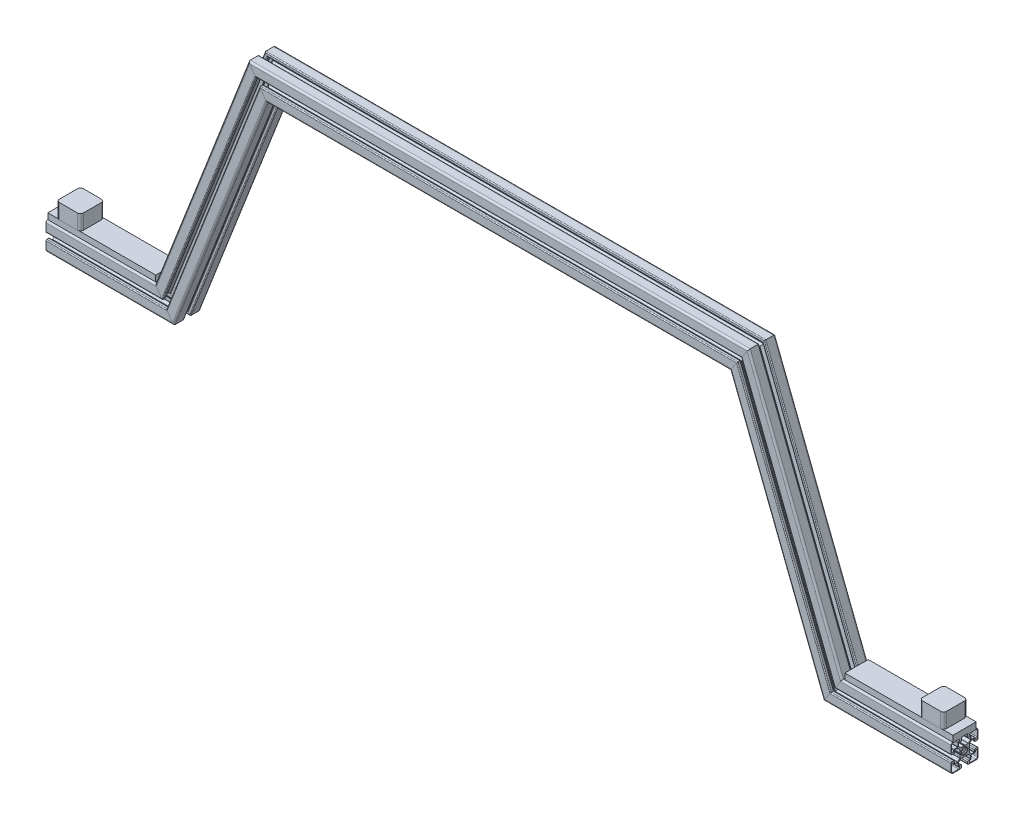
SolidWorks part; units mm, degrees
material "Commercially Pure CP-Ti UNS R50400 (SS)"
ref_plane "Front Plane" through (0, 0, 0) normal (0, 0, 1) x (1, 0, 0)
ref_plane "Top Plane" through (0, 0, 0) normal (0, 1, 0) x (1, 0, 0)
ref_plane "Right Plane" through (0, 0, 0) normal (1, 0, 0) x (0, 0, -1)
sketch "Sketch5" plane through (0, 0, 0) normal (1, 0, 0) x (0, 0, -1)
  line L0 (13.9698, 21.2743) -> (13.5298, 21.2743)
  line L1 (12.0298, 22.7743) -> (12.0298, 23.2743)
  line L2 (13.5298, 24.7743) -> (23.1398, 24.7743)
  line L3 (25.4198, 22.4943) -> (25.4198, 12.8843)
  line L4 (23.9198, 11.3843) -> (23.4198, 11.3843)
  line L5 (21.9198, 12.8843) -> (21.9198, 13.3243)
  line L6 (20.9198, 14.3243) -> (15.3498, 14.3243)
  line L7 (14.9698, 14.7043) -> (14.9698, 20.2743)
  line L8 (21.9589, -6.6897) -> (21.9589, -6.2497)
  line L9 (23.4589, -4.7497) -> (23.9589, -4.7497)
  line L10 (25.4589, -6.2497) -> (25.4589, -15.8597)
  line L11 (23.1789, -18.1397) -> (13.5689, -18.1397)
  line L12 (12.0689, -16.6397) -> (12.0689, -16.1397)
  line L13 (13.5689, -14.6397) -> (14.0089, -14.6397)
  line L14 (15.0089, -13.6397) -> (15.0089, -8.0697)
  line L15 (15.3889, -7.6897) -> (20.9589, -7.6897)
  line L16 (-6.0052, -14.6787) -> (-5.5652, -14.6787)
  line L17 (-4.0652, -16.1787) -> (-4.0652, -16.6787)
  line L18 (-5.5652, -18.1787) -> (-15.1752, -18.1787)
  line L19 (-17.4552, -15.8987) -> (-17.4552, -6.2887)
  line L20 (-15.9552, -4.7887) -> (-15.4552, -4.7887)
  line L21 (-13.9552, -6.2887) -> (-13.9552, -6.7287)
  line L22 (-12.9552, -7.7287) -> (-7.3852, -7.7287)
  line L23 (-7.0052, -8.1087) -> (-7.0052, -13.6787)
  line L24 (1.8289, -2.4886) -> (1.4132, -2.3164)
  line L25 (-1.632, 0.7289) -> (-1.8042, 1.1447)
  line L26 (-1.804, 5.4512) -> (-1.6318, 5.867)
  line L27 (1.4134, 8.9121) -> (1.8292, 9.0843)
  line L28 (6.1358, 9.0842) -> (6.5515, 8.912)
  line L29 (9.5966, 5.8667) -> (9.7688, 5.451)
  line L30 (9.7687, 1.1444) -> (9.5965, 0.7287)
  line L31 (6.5512, -2.3165) -> (6.1355, -2.4887)
  line L32 (-13.9942, 13.2853) -> (-13.9942, 12.8453)
  line L33 (-15.4942, 11.3453) -> (-15.9942, 11.3453)
  line L34 (-17.4942, 12.8453) -> (-17.4942, 22.4553)
  line L35 (-15.2142, 24.7353) -> (-5.6042, 24.7353)
  line L36 (-4.1042, 23.2353) -> (-4.1042, 22.7353)
  line L37 (-5.6042, 21.2353) -> (-6.0442, 21.2353)
  line L38 (-7.0442, 20.2353) -> (-7.0442, 14.6653)
  line L39 (-7.4242, 14.2853) -> (-12.9942, 14.2853)
  line L40 (4.9058, 11.2153) -> (4.0058, 10.7002)
  line L41 (4.0058, 10.7002) -> (3.1058, 11.2153)
  line L42 (3.1058, 11.2153) -> (-2.1975, 11.2153)
  line L43 (-2.4662, 11.3266) -> (-5.9329, 14.7933)
  line L44 (-6.0442, 15.062) -> (-6.0442, 19.3553)
  line L45 (-5.6642, 19.7353) -> (-2.5792, 19.7353)
  line L46 (-1.0592, 21.2553) -> (-1.0592, 24.2153)
  line L47 (-2.5792, 25.7353) -> (-15.4942, 25.7353)
  line L48 (-18.4942, 22.7353) -> (-18.4942, 9.8203)
  line L49 (-16.9742, 8.3003) -> (-14.0142, 8.3003)
  line L50 (-12.4942, 9.8203) -> (-12.4942, 12.9053)
  line L51 (-12.1142, 13.2853) -> (-7.8138, 13.2853)
  line L52 (-7.5451, 13.174) -> (-4.0855, 9.7144)
  line L53 (-3.9742, 9.4457) -> (-3.9742, 4.1353)
  line L54 (-3.9742, 4.1353) -> (-3.4546, 3.2353)
  line L55 (-3.4546, 3.2353) -> (-3.9742, 2.3353)
  line L56 (-3.9742, 2.3353) -> (-3.9742, -2.968)
  line L57 (-4.0855, -3.2367) -> (-7.5522, -6.7034)
  line L58 (-7.8209, -6.8147) -> (-12.1142, -6.8147)
  line L59 (-12.4942, -6.4347) -> (-12.4942, -3.3497)
  line L60 (-14.0142, -1.8297) -> (-16.9742, -1.8297)
  line L61 (-18.4942, -3.3497) -> (-18.4942, -16.2647)
  line L62 (-15.4942, -19.2647) -> (-2.5792, -19.2647)
  line L63 (-1.0592, -17.7447) -> (-1.0592, -14.7847)
  line L64 (-2.5792, -13.2647) -> (-5.6642, -13.2647)
  line L65 (-6.0442, -12.8847) -> (-6.0442, -8.5843)
  line L66 (-5.9329, -8.3156) -> (-2.4733, -4.856)
  line L67 (-2.2046, -4.7447) -> (3.1058, -4.7447)
  line L68 (3.1058, -4.7447) -> (4.0058, -4.2295)
  line L69 (4.0058, -4.2295) -> (4.9058, -4.7447)
  line L70 (4.9058, -4.7447) -> (10.2091, -4.7447)
  line L71 (10.4778, -4.856) -> (13.9445, -8.3227)
  line L72 (14.0558, -8.5914) -> (14.0558, -12.8847)
  line L73 (13.6758, -13.2647) -> (10.5908, -13.2647)
  line L74 (9.0708, -14.7847) -> (9.0708, -17.7447)
  line L75 (10.5908, -19.2647) -> (23.5058, -19.2647)
  line L76 (26.5058, -16.2647) -> (26.5058, -3.3497)
  line L77 (24.9858, -1.8297) -> (22.0258, -1.8297)
  line L78 (20.5058, -3.3497) -> (20.5058, -6.4347)
  line L79 (20.1258, -6.8147) -> (15.8254, -6.8147)
  line L80 (15.5567, -6.7034) -> (12.0971, -3.2438)
  line L81 (11.9858, -2.9751) -> (11.9858, 2.3353)
  line L82 (11.9858, 2.3353) -> (11.4662, 3.2353)
  line L83 (11.4662, 3.2353) -> (11.9858, 4.1353)
  line L84 (11.9858, 4.1353) -> (11.9858, 9.4386)
  line L85 (12.0971, 9.7073) -> (15.5638, 13.174)
  line L86 (15.8325, 13.2853) -> (20.1258, 13.2853)
  line L87 (20.5058, 12.9053) -> (20.5058, 9.8203)
  line L88 (22.0258, 8.3003) -> (24.9858, 8.3003)
  line L89 (26.5058, 9.8203) -> (26.5058, 22.7353)
  line L90 (23.5058, 25.7353) -> (10.5908, 25.7353)
  line L91 (9.0708, 24.2153) -> (9.0708, 21.2553)
  line L92 (10.5908, 19.7353) -> (13.6758, 19.7353)
  line L93 (14.0558, 19.3553) -> (14.0558, 15.0549)
  line L94 (13.9445, 14.7862) -> (10.4849, 11.3266)
  line L95 (10.2162, 11.2153) -> (4.9058, 11.2153)
  arc A0 (14.9698, 20.2743) -> (13.9698, 21.2743) centre (13.9698, 20.2743) ccw
  arc A1 (12.0298, 22.7743) -> (13.5298, 21.2743) centre (13.5298, 22.7743) ccw
  arc A2 (13.5298, 24.7743) -> (12.0298, 23.2743) centre (13.5298, 23.2743) ccw
  arc A3 (25.4198, 22.4943) -> (23.1398, 24.7743) centre (23.1398, 22.4943) ccw
  arc A4 (23.9198, 11.3843) -> (25.4198, 12.8843) centre (23.9198, 12.8843) ccw
  arc A5 (21.9198, 12.8843) -> (23.4198, 11.3843) centre (23.4198, 12.8843) ccw
  arc A6 (21.9198, 13.3243) -> (20.9198, 14.3243) centre (20.9198, 13.3243) ccw
  arc A7 (14.9698, 14.7043) -> (15.3498, 14.3243) centre (15.3498, 14.7043) ccw
  arc A8 (20.9589, -7.6897) -> (21.9589, -6.6897) centre (20.9589, -6.6897) ccw
  arc A9 (23.4589, -4.7497) -> (21.9589, -6.2497) centre (23.4589, -6.2497) ccw
  arc A10 (25.4589, -6.2497) -> (23.9589, -4.7497) centre (23.9589, -6.2497) ccw
  arc A11 (23.1789, -18.1397) -> (25.4589, -15.8597) centre (23.1789, -15.8597) ccw
  arc A12 (12.0689, -16.6397) -> (13.5689, -18.1397) centre (13.5689, -16.6397) ccw
  arc A13 (13.5689, -14.6397) -> (12.0689, -16.1397) centre (13.5689, -16.1397) ccw
  arc A14 (14.0089, -14.6397) -> (15.0089, -13.6397) centre (14.0089, -13.6397) ccw
  arc A15 (15.3889, -7.6897) -> (15.0089, -8.0697) centre (15.3889, -8.0697) ccw
  arc A16 (-7.0052, -13.6787) -> (-6.0052, -14.6787) centre (-6.0052, -13.6787) ccw
  arc A17 (-4.0652, -16.1787) -> (-5.5652, -14.6787) centre (-5.5652, -16.1787) ccw
  arc A18 (-5.5652, -18.1787) -> (-4.0652, -16.6787) centre (-5.5652, -16.6787) ccw
  arc A19 (-17.4552, -15.8987) -> (-15.1752, -18.1787) centre (-15.1752, -15.8987) ccw
  arc A20 (-15.9552, -4.7887) -> (-17.4552, -6.2887) centre (-15.9552, -6.2887) ccw
  arc A21 (-13.9552, -6.2887) -> (-15.4552, -4.7887) centre (-15.4552, -6.2887) ccw
  arc A22 (-13.9552, -6.7287) -> (-12.9552, -7.7287) centre (-12.9552, -6.7287) ccw
  arc A23 (-7.0052, -8.1087) -> (-7.3852, -7.7287) centre (-7.3852, -8.1087) ccw
  arc A24 (1.0363, -0.7421) -> (1.4132, -2.3164) centre (1.7959, -1.3925) ccw
  arc A25 (-0.0577, 0.352) -> (1.0363, -0.7421) centre (3.9823, 3.2978) ccw
  arc A26 (-1.632, 0.7289) -> (-0.0577, 0.352) centre (-0.7081, 1.1116) ccw
  arc A27 (-0.9575, 2.5244) -> (-1.8042, 1.1447) centre (-0.8803, 1.5274) ccw
  arc A28 (-0.9574, 4.0715) -> (-0.9575, 2.5244) centre (3.9823, 3.2978) ccw
  arc A29 (-1.804, 5.4512) -> (-0.9574, 4.0715) centre (-0.8802, 5.0686) ccw
  arc A30 (-0.0575, 6.2439) -> (-1.6318, 5.867) centre (-0.708, 5.4843) ccw
  arc A31 (1.0365, 7.3379) -> (-0.0575, 6.2439) centre (3.9823, 3.2978) ccw
  arc A32 (1.4134, 8.9121) -> (1.0365, 7.3379) centre (1.7961, 7.9882) ccw
  arc A33 (3.2089, 8.2376) -> (1.8292, 9.0843) centre (2.2119, 8.1604) ccw
  arc A34 (4.7561, 8.2376) -> (3.2089, 8.2376) centre (3.9823, 3.2978) ccw
  arc A35 (6.1358, 9.0842) -> (4.7561, 8.2376) centre (5.7531, 8.1603) ccw
  arc A36 (6.9284, 7.3377) -> (6.5515, 8.912) centre (6.1688, 7.9881) ccw
  arc A37 (8.0224, 6.2437) -> (6.9284, 7.3377) centre (3.9823, 3.2978) ccw
  arc A38 (9.5966, 5.8667) -> (8.0224, 6.2437) centre (8.6727, 5.484) ccw
  arc A39 (8.9222, 4.0713) -> (9.7688, 5.451) centre (8.845, 5.0683) ccw
  arc A40 (8.9221, 2.5241) -> (8.9222, 4.0713) centre (3.9823, 3.2978) ccw
  arc A41 (9.7687, 1.1444) -> (8.9221, 2.5241) centre (8.8448, 1.5271) ccw
  arc A42 (8.0222, 0.3518) -> (9.5965, 0.7287) centre (8.6726, 1.1113) ccw
  arc A43 (6.9282, -0.7422) -> (8.0222, 0.3518) centre (3.9823, 3.2978) ccw
  arc A44 (6.5512, -2.3165) -> (6.9282, -0.7422) centre (6.1685, -1.3926) ccw
  arc A45 (4.7558, -1.642) -> (6.1355, -2.4887) centre (5.7528, -1.5648) ccw
  arc A46 (3.2086, -1.642) -> (4.7558, -1.642) centre (3.9823, 3.2978) ccw
  arc A47 (1.8289, -2.4886) -> (3.2086, -1.642) centre (2.2116, -1.5647) ccw
  arc A48 (-12.9942, 14.2853) -> (-13.9942, 13.2853) centre (-12.9942, 13.2853) ccw
  arc A49 (-15.4942, 11.3453) -> (-13.9942, 12.8453) centre (-15.4942, 12.8453) ccw
  arc A50 (-17.4942, 12.8453) -> (-15.9942, 11.3453) centre (-15.9942, 12.8453) ccw
  arc A51 (-15.2142, 24.7353) -> (-17.4942, 22.4553) centre (-15.2142, 22.4553) ccw
  arc A52 (-4.1042, 23.2353) -> (-5.6042, 24.7353) centre (-5.6042, 23.2353) ccw
  arc A53 (-5.6042, 21.2353) -> (-4.1042, 22.7353) centre (-5.6042, 22.7353) ccw
  arc A54 (-6.0442, 21.2353) -> (-7.0442, 20.2353) centre (-6.0442, 20.2353) ccw
  arc A55 (-7.4242, 14.2853) -> (-7.0442, 14.6653) centre (-7.4242, 14.6653) ccw
  arc A56 (-2.4662, 11.3266) -> (-2.1975, 11.2153) centre (-2.1975, 11.5953) ccw
  arc A57 (-6.0442, 15.062) -> (-5.9329, 14.7933) centre (-5.6642, 15.062) ccw
  arc A58 (-5.6642, 19.7353) -> (-6.0442, 19.3553) centre (-5.6642, 19.3553) ccw
  arc A59 (-2.5792, 19.7353) -> (-1.0592, 21.2553) centre (-2.5792, 21.2553) ccw
  arc A60 (-1.0592, 24.2153) -> (-2.5792, 25.7353) centre (-2.5792, 24.2153) ccw
  arc A61 (-15.4942, 25.7353) -> (-18.4942, 22.7353) centre (-15.4942, 22.7353) ccw
  arc A62 (-18.4942, 9.8203) -> (-16.9742, 8.3003) centre (-16.9742, 9.8203) ccw
  arc A63 (-14.0142, 8.3003) -> (-12.4942, 9.8203) centre (-14.0142, 9.8203) ccw
  arc A64 (-12.1142, 13.2853) -> (-12.4942, 12.9053) centre (-12.1142, 12.9053) ccw
  arc A65 (-7.5451, 13.174) -> (-7.8138, 13.2853) centre (-7.8138, 12.9053) ccw
  arc A66 (-3.9742, 9.4457) -> (-4.0855, 9.7144) centre (-4.3542, 9.4457) ccw
  arc A67 (-4.0855, -3.2367) -> (-3.9742, -2.968) centre (-4.3542, -2.968) ccw
  arc A68 (-7.8209, -6.8147) -> (-7.5522, -6.7034) centre (-7.8209, -6.4347) ccw
  arc A69 (-12.4942, -6.4347) -> (-12.1142, -6.8147) centre (-12.1142, -6.4347) ccw
  arc A70 (-12.4942, -3.3497) -> (-14.0142, -1.8297) centre (-14.0142, -3.3497) ccw
  arc A71 (-16.9742, -1.8297) -> (-18.4942, -3.3497) centre (-16.9742, -3.3497) ccw
  arc A72 (-18.4942, -16.2647) -> (-15.4942, -19.2647) centre (-15.4942, -16.2647) ccw
  arc A73 (-2.5792, -19.2647) -> (-1.0592, -17.7447) centre (-2.5792, -17.7447) ccw
  arc A74 (-1.0592, -14.7847) -> (-2.5792, -13.2647) centre (-2.5792, -14.7847) ccw
  arc A75 (-6.0442, -12.8847) -> (-5.6642, -13.2647) centre (-5.6642, -12.8847) ccw
  arc A76 (-5.9329, -8.3156) -> (-6.0442, -8.5843) centre (-5.6642, -8.5843) ccw
  arc A77 (-2.2046, -4.7447) -> (-2.4733, -4.856) centre (-2.2046, -5.1247) ccw
  arc A78 (10.4778, -4.856) -> (10.2091, -4.7447) centre (10.2091, -5.1247) ccw
  arc A79 (14.0558, -8.5914) -> (13.9445, -8.3227) centre (13.6758, -8.5914) ccw
  arc A80 (13.6758, -13.2647) -> (14.0558, -12.8847) centre (13.6758, -12.8847) ccw
  arc A81 (10.5908, -13.2647) -> (9.0708, -14.7847) centre (10.5908, -14.7847) ccw
  arc A82 (9.0708, -17.7447) -> (10.5908, -19.2647) centre (10.5908, -17.7447) ccw
  arc A83 (23.5058, -19.2647) -> (26.5058, -16.2647) centre (23.5058, -16.2647) ccw
  arc A84 (26.5058, -3.3497) -> (24.9858, -1.8297) centre (24.9858, -3.3497) ccw
  arc A85 (22.0258, -1.8297) -> (20.5058, -3.3497) centre (22.0258, -3.3497) ccw
  arc A86 (20.1258, -6.8147) -> (20.5058, -6.4347) centre (20.1258, -6.4347) ccw
  arc A87 (15.5567, -6.7034) -> (15.8254, -6.8147) centre (15.8254, -6.4347) ccw
  arc A88 (11.9858, -2.9751) -> (12.0971, -3.2438) centre (12.3658, -2.9751) ccw
  arc A89 (12.0971, 9.7073) -> (11.9858, 9.4386) centre (12.3658, 9.4386) ccw
  arc A90 (15.8325, 13.2853) -> (15.5638, 13.174) centre (15.8325, 12.9053) ccw
  arc A91 (20.5058, 12.9053) -> (20.1258, 13.2853) centre (20.1258, 12.9053) ccw
  arc A92 (20.5058, 9.8203) -> (22.0258, 8.3003) centre (22.0258, 9.8203) ccw
  arc A93 (24.9858, 8.3003) -> (26.5058, 9.8203) centre (24.9858, 9.8203) ccw
  arc A94 (26.5058, 22.7353) -> (23.5058, 25.7353) centre (23.5058, 22.7353) ccw
  arc A95 (10.5908, 25.7353) -> (9.0708, 24.2153) centre (10.5908, 24.2153) ccw
  arc A96 (9.0708, 21.2553) -> (10.5908, 19.7353) centre (10.5908, 21.2553) ccw
  arc A97 (14.0558, 19.3553) -> (13.6758, 19.7353) centre (13.6758, 19.3553) ccw
  arc A98 (13.9445, 14.7862) -> (14.0558, 15.0549) centre (13.6758, 15.0549) ccw
  arc A99 (10.2162, 11.2153) -> (10.4849, 11.3266) centre (10.2162, 11.5953) ccw
sketch "Sketch1" plane through (0, 0, 0) normal (0, 0, 1) x (1, 0, 0)
  line L0 (0, 0) -> (200, 0)
  line L1 (200, 0) -> (355.8974, 400)
  line L2 (355.8974, 400) -> (755.8974, 400)
  dimension "D1" = 400
  dimension "D2" = 200
  dimension "D3" = 400
sketch "Sketch2" [suppressed] plane through (0, 0, 0) normal (1, 0, 0) x (0, 0, -1)
  line L0 (-33.5, -41) -> (-31.5, -41)
  line L1 (-31.5, -43) -> (-42, -43)
  line L2 (-43, -42) -> (-43, -31.5)
  line L3 (-41, -31.5) -> (-41, -33.5)
  line L4 (-40, -34.5) -> (-34.88, -34.5)
  line L5 (-34.5, -34.88) -> (-34.5, -40)
  line L6 (-16.657, -26.2238) -> (-18.284, -25.188)
  line L7 (-19.8123, -26.7162) -> (-18.7764, -28.3429)
  line L8 (-21.0015, -29.2647) -> (-21.4195, -27.3819)
  line L9 (-23.5808, -27.3818) -> (-23.9986, -29.2645)
  line L10 (-26.2238, -28.343) -> (-25.188, -26.716)
  line L11 (-26.7162, -25.1877) -> (-28.3429, -26.2236)
  line L12 (-29.2647, -23.9985) -> (-27.3819, -23.5805)
  line L13 (-27.3818, -21.4192) -> (-29.2645, -21.0014)
  line L14 (-28.343, -18.7762) -> (-26.716, -19.812)
  line L15 (-25.1877, -18.2838) -> (-26.2236, -16.6571)
  line L16 (-23.9985, -15.7353) -> (-23.5805, -17.6181)
  line L17 (-21.4192, -17.6182) -> (-21.0014, -15.7355)
  line L18 (-18.7762, -16.657) -> (-19.812, -18.284)
  line L19 (-18.2838, -19.8123) -> (-16.6571, -18.7764)
  line L20 (-15.7353, -21.0015) -> (-17.6181, -21.4195)
  line L21 (-17.6182, -23.5808) -> (-15.7355, -23.9986)
  line L22 (41, -33.5) -> (41, -31.5)
  line L23 (43, -31.5) -> (43, -42)
  line L24 (42, -43) -> (31.5, -43)
  line L25 (31.5, -41) -> (33.5, -41)
  line L26 (34.5, -40) -> (34.5, -34.88)
  line L27 (34.88, -34.5) -> (40, -34.5)
  line L28 (26.7162, -19.8123) -> (28.3429, -18.7764)
  line L29 (29.2647, -21.0015) -> (27.3819, -21.4195)
  line L30 (27.3818, -23.5808) -> (29.2645, -23.9986)
  line L31 (28.343, -26.2238) -> (26.716, -25.188)
  line L32 (25.1877, -26.7162) -> (26.2236, -28.3429)
  line L33 (23.9985, -29.2647) -> (23.5805, -27.3819)
  line L34 (21.4192, -27.3818) -> (21.0014, -29.2645)
  line L35 (18.7762, -28.343) -> (19.812, -26.716)
  line L36 (18.2838, -25.1877) -> (16.6571, -26.2236)
  line L37 (15.7353, -23.9985) -> (17.6181, -23.5805)
  line L38 (17.6182, -21.4192) -> (15.7355, -21.0014)
  line L39 (16.657, -18.7762) -> (18.284, -19.812)
  line L40 (19.8123, -18.2838) -> (18.7764, -16.6571)
  line L41 (21.0015, -15.7353) -> (21.4195, -17.6181)
  line L42 (23.5808, -17.6182) -> (23.9986, -15.7355)
  line L43 (26.2238, -16.657) -> (25.188, -18.284)
  line L44 (34.5, 34.88) -> (34.5, 40)
  line L45 (33.5, 41) -> (31.5, 41)
  line L46 (31.5, 43) -> (42, 43)
  line L47 (43, 42) -> (43, 31.5)
  line L48 (41, 31.5) -> (41, 33.5)
  line L49 (40, 34.5) -> (34.88, 34.5)
  line L50 (26.7162, 25.1877) -> (28.3429, 26.2236)
  line L51 (29.2647, 23.9985) -> (27.3819, 23.5805)
  line L52 (27.3818, 21.4192) -> (29.2645, 21.0014)
  line L53 (28.343, 18.7762) -> (26.716, 19.812)
  line L54 (25.1877, 18.2838) -> (26.2236, 16.6571)
  line L55 (23.9985, 15.7353) -> (23.5805, 17.6181)
  line L56 (21.4192, 17.6182) -> (21.0014, 15.7355)
  line L57 (18.7762, 16.657) -> (19.812, 18.284)
  line L58 (18.2838, 19.8123) -> (16.6571, 18.7764)
  line L59 (15.7353, 21.0015) -> (17.6181, 21.4195)
  line L60 (17.6182, 23.5808) -> (15.7355, 23.9986)
  line L61 (16.657, 26.2238) -> (18.284, 25.188)
  line L62 (19.8123, 26.7162) -> (18.7764, 28.3429)
  line L63 (21.0015, 29.2647) -> (21.4195, 27.3819)
  line L64 (23.5808, 27.3818) -> (23.9986, 29.2645)
  line L65 (26.2238, 28.343) -> (25.188, 26.716)
  line L66 (-41, 33.5) -> (-41, 31.5)
  line L67 (-43, 31.5) -> (-43, 42)
  line L68 (-42, 43) -> (-31.5, 43)
  line L69 (-31.5, 41) -> (-33.5, 41)
  line L70 (-34.5, 40) -> (-34.5, 34.88)
  line L71 (-34.88, 34.5) -> (-40, 34.5)
  line L72 (-16.657, 18.7762) -> (-18.284, 19.812)
  line L73 (-19.8123, 18.2838) -> (-18.7764, 16.6571)
  line L74 (-21.0015, 15.7353) -> (-21.4195, 17.6181)
  line L75 (-23.5808, 17.6182) -> (-23.9986, 15.7355)
  line L76 (-26.2238, 16.657) -> (-25.188, 18.284)
  line L77 (-26.7162, 19.8123) -> (-28.3429, 18.7764)
  line L78 (-29.2647, 21.0015) -> (-27.3819, 21.4195)
  line L79 (-27.3818, 23.5808) -> (-29.2645, 23.9986)
  line L80 (-28.343, 26.2238) -> (-26.716, 25.188)
  line L81 (-25.1877, 26.7162) -> (-26.2236, 28.3429)
  line L82 (-23.9985, 29.2647) -> (-23.5805, 27.3819)
  line L83 (-21.4192, 27.3818) -> (-21.0014, 29.2645)
  line L84 (-18.7762, 28.343) -> (-19.812, 26.716)
  line L85 (-18.2838, 25.1877) -> (-16.6571, 26.2236)
  line L86 (-15.7353, 23.9985) -> (-17.6181, 23.5805)
  line L87 (-17.6182, 21.4192) -> (-15.7355, 21.0014)
  line L88 (39, -10.16) -> (33.3774, -10.16)
  line L89 (31.9632, -10.7458) -> (29.8203, -12.8887)
  line L90 (29.5516, -13) -> (23.4, -13)
  line L91 (23.4, -13) -> (22.5, -13.5151)
  line L92 (22.5, -13.5151) -> (21.6, -13)
  line L93 (21.6, -13) -> (15, -13)
  line L94 (13, -15) -> (13, -21.6)
  line L95 (13, -21.6) -> (13.5196, -22.5)
  line L96 (13.5196, -22.5) -> (13, -23.4)
  line L97 (13, -23.4) -> (13, -29.5516)
  line L98 (12.8887, -29.8203) -> (11.3787, -31.3303)
  line L99 (10.5, -33.4516) -> (10.5, -40)
  line L100 (11.5, -41) -> (13.5, -41)
  line L101 (13.5, -43) -> (-13.5, -43)
  line L102 (-13.5, -41) -> (-11.5, -41)
  line L103 (-10.5, -40) -> (-10.5, -33.4516)
  line L104 (-11.3787, -31.3303) -> (-12.8887, -29.8203)
  line L105 (-13, -29.5516) -> (-13, -23.4)
  line L106 (-13, -23.4) -> (-13.5196, -22.5)
  line L107 (-13.5196, -22.5) -> (-13, -21.6)
  line L108 (-13, -21.6) -> (-13, -15)
  line L109 (-15, -13) -> (-21.6, -13)
  line L110 (-21.6, -13) -> (-22.5, -13.5151)
  line L111 (-22.5, -13.5151) -> (-23.4, -13)
  line L112 (-23.4, -13) -> (-29.5516, -13)
  line L113 (-29.8203, -12.8887) -> (-31.9632, -10.7458)
  line L114 (-33.3774, -10.16) -> (-39, -10.16)
  line L115 (-41, -12.16) -> (-41, -13.5)
  line L116 (-43, -13.5) -> (-43, 13.5)
  line L117 (-41, 13.5) -> (-41, 12.16)
  line L118 (-39, 10.16) -> (-33.3774, 10.16)
  line L119 (-31.9632, 10.7458) -> (-29.8203, 12.8887)
  line L120 (-29.5516, 13) -> (-23.4, 13)
  line L121 (-23.4, 13) -> (-22.5, 13.5151)
  line L122 (-22.5, 13.5151) -> (-21.6, 13)
  line L123 (-21.6, 13) -> (-15, 13)
  line L124 (-13, 15) -> (-13, 21.6)
  line L125 (-13, 21.6) -> (-13.5196, 22.5)
  line L126 (-13.5196, 22.5) -> (-13, 23.4)
  line L127 (-13, 23.4) -> (-13, 29.5516)
  line L128 (-12.8887, 29.8203) -> (-11.3787, 31.3303)
  line L129 (-10.5, 33.4516) -> (-10.5, 40)
  line L130 (-11.5, 41) -> (-13.5, 41)
  line L131 (-13.5, 43) -> (13.5, 43)
  line L132 (13.5, 41) -> (11.5, 41)
  line L133 (10.5, 40) -> (10.5, 33.4516)
  line L134 (11.3787, 31.3303) -> (12.8887, 29.8203)
  line L135 (13, 29.5516) -> (13, 23.4)
  line L136 (13, 23.4) -> (13.5196, 22.5)
  line L137 (13.5196, 22.5) -> (13, 21.6)
  line L138 (13, 21.6) -> (13, 15)
  line L139 (15, 13) -> (21.6, 13)
  line L140 (21.6, 13) -> (22.5, 13.5151)
  line L141 (22.5, 13.5151) -> (23.4, 13)
  line L142 (23.4, 13) -> (29.5516, 13)
  line L143 (29.8203, 12.8887) -> (31.9581, 10.7509)
  line L144 (33.3723, 10.1651) -> (39, 10.1651)
  line L145 (41, 12.1651) -> (41, 13.5)
  line L146 (43, 13.5) -> (43, -13.5)
  line L147 (41, -13.5) -> (41, -12.16)
  line L148 (45, -15.915) -> (45, 15.915)
  line L149 (43.48, 17.435) -> (40.52, 17.435)
  line L150 (39, 15.915) -> (39, 13.45)
  line L151 (38, 12.45) -> (34.9984, 12.45)
  line L152 (34.7297, 12.5613) -> (32.1113, 15.1797)
  line L153 (32, 15.4484) -> (32, 21.6)
  line L154 (32, 21.6) -> (31.4804, 22.5)
  line L155 (31.4804, 22.5) -> (32, 23.4)
  line L156 (32, 23.4) -> (32, 29.5516)
  line L157 (32.1113, 29.8203) -> (34.7297, 32.4387)
  line L158 (34.9984, 32.55) -> (38, 32.55)
  line L159 (39, 31.55) -> (39, 29.085)
  line L160 (40.52, 27.565) -> (43.48, 27.565)
  line L161 (45, 29.085) -> (45, 42)
  line L162 (42, 45) -> (29.085, 45)
  line L163 (27.565, 43.48) -> (27.565, 40.52)
  line L164 (29.085, 39) -> (31.55, 39)
  line L165 (32.55, 38) -> (32.55, 34.9984)
  line L166 (32.4387, 34.7297) -> (29.8203, 32.1113)
  line L167 (29.5516, 32) -> (23.4, 32)
  line L168 (23.4, 32) -> (22.5, 31.4849)
  line L169 (22.5, 31.4849) -> (21.6, 32)
  line L170 (21.6, 32) -> (15.4484, 32)
  line L171 (15.1797, 32.1113) -> (12.5613, 34.7297)
  line L172 (12.45, 34.9984) -> (12.45, 38)
  line L173 (13.45, 39) -> (15.915, 39)
  line L174 (17.435, 40.52) -> (17.435, 43.48)
  line L175 (15.915, 45) -> (-15.915, 45)
  line L176 (-17.435, 43.48) -> (-17.435, 40.52)
  line L177 (-15.915, 39) -> (-13.45, 39)
  line L178 (-12.45, 38) -> (-12.45, 34.9984)
  line L179 (-12.5613, 34.7297) -> (-15.1797, 32.1113)
  line L180 (-15.4484, 32) -> (-21.6, 32)
  line L181 (-21.6, 32) -> (-22.5, 31.4849)
  line L182 (-22.5, 31.4849) -> (-23.4, 32)
  line L183 (-23.4, 32) -> (-29.5516, 32)
  line L184 (-29.8203, 32.1113) -> (-32.4387, 34.7297)
  line L185 (-32.55, 34.9984) -> (-32.55, 38)
  line L186 (-31.55, 39) -> (-29.085, 39)
  line L187 (-27.565, 40.52) -> (-27.565, 43.48)
  line L188 (-29.085, 45) -> (-42, 45)
  line L189 (-45, 42) -> (-45, 29.085)
  line L190 (-43.48, 27.565) -> (-40.52, 27.565)
  line L191 (-39, 29.085) -> (-39, 31.55)
  line L192 (-38, 32.55) -> (-34.9984, 32.55)
  line L193 (-34.7297, 32.4387) -> (-32.1113, 29.8203)
  line L194 (-32, 29.5516) -> (-32, 23.4)
  line L195 (-32, 23.4) -> (-31.4804, 22.5)
  line L196 (-31.4804, 22.5) -> (-32, 21.6)
  line L197 (-32, 21.6) -> (-32, 15.4484)
  line L198 (-32.1113, 15.1797) -> (-34.7297, 12.5613)
  line L199 (-34.9984, 12.45) -> (-38, 12.45)
  line L200 (-39, 13.45) -> (-39, 15.915)
  line L201 (-40.52, 17.435) -> (-43.48, 17.435)
  line L202 (-45, 15.915) -> (-45, -15.915)
  line L203 (-43.48, -17.435) -> (-40.52, -17.435)
  line L204 (-39, -15.915) -> (-39, -13.45)
  line L205 (-38, -12.45) -> (-34.9984, -12.45)
  line L206 (-34.7297, -12.5613) -> (-32.1113, -15.1797)
  line L207 (-32, -15.4484) -> (-32, -21.6)
  line L208 (-32, -21.6) -> (-31.4804, -22.5)
  line L209 (-31.4804, -22.5) -> (-32, -23.4)
  line L210 (-32, -23.4) -> (-32, -29.5516)
  line L211 (-32.1113, -29.8203) -> (-34.7297, -32.4387)
  line L212 (-34.9984, -32.55) -> (-38, -32.55)
  line L213 (-39, -31.55) -> (-39, -29.085)
  line L214 (-40.52, -27.565) -> (-43.48, -27.565)
  line L215 (-45, -29.085) -> (-45, -42)
  line L216 (-42, -45) -> (-29.085, -45)
  line L217 (-27.565, -43.48) -> (-27.565, -40.52)
  line L218 (-29.085, -39) -> (-31.55, -39)
  line L219 (-32.55, -38) -> (-32.55, -34.9984)
  line L220 (-32.4387, -34.7297) -> (-29.8203, -32.1113)
  line L221 (-29.5516, -32) -> (-23.4, -32)
  line L222 (-23.4, -32) -> (-22.5, -31.4849)
  line L223 (-22.5, -31.4849) -> (-21.6, -32)
  line L224 (-21.6, -32) -> (-15.4484, -32)
  line L225 (-15.1797, -32.1113) -> (-12.5613, -34.7297)
  line L226 (-12.45, -34.9984) -> (-12.45, -38)
  line L227 (-13.45, -39) -> (-15.915, -39)
  line L228 (-17.435, -40.52) -> (-17.435, -43.48)
  line L229 (-15.915, -45) -> (15.915, -45)
  line L230 (17.435, -43.48) -> (17.435, -40.52)
  line L231 (15.915, -39) -> (13.45, -39)
  line L232 (12.45, -38) -> (12.45, -34.9984)
  line L233 (12.5613, -34.7297) -> (15.1797, -32.1113)
  line L234 (15.4484, -32) -> (21.6, -32)
  line L235 (21.6, -32) -> (22.5, -31.4849)
  line L236 (22.5, -31.4849) -> (23.4, -32)
  line L237 (23.4, -32) -> (29.5516, -32)
  line L238 (29.8203, -32.1113) -> (32.4387, -34.7297)
  line L239 (32.55, -34.9984) -> (32.55, -38)
  line L240 (31.55, -39) -> (29.085, -39)
  line L241 (27.565, -40.52) -> (27.565, -43.48)
  line L242 (29.085, -45) -> (42, -45)
  line L243 (45, -42) -> (45, -29.085)
  line L244 (43.48, -27.565) -> (40.52, -27.565)
  line L245 (39, -29.085) -> (39, -31.55)
  line L246 (38, -32.55) -> (34.9984, -32.55)
  line L247 (34.7297, -32.4387) -> (32.1113, -29.8203)
  line L248 (32, -29.5516) -> (32, -23.4)
  line L249 (32, -23.4) -> (31.4804, -22.5)
  line L250 (31.4804, -22.5) -> (32, -21.6)
  line L251 (32, -21.6) -> (32, -15.4484)
  line L252 (32.1113, -15.1797) -> (34.7297, -12.5613)
  line L253 (34.9984, -12.45) -> (38, -12.45)
  line L254 (39, -13.45) -> (39, -15.915)
  line L255 (40.52, -17.435) -> (43.48, -17.435)
  arc A0 (-34.5, -40) -> (-33.5, -41) centre (-33.5, -40) ccw
  arc A1 (-31.5, -43) -> (-31.5, -41) centre (-31.5, -42) ccw
  arc A2 (-43, -42) -> (-42, -43) centre (-42, -42) ccw
  arc A3 (-41, -31.5) -> (-43, -31.5) centre (-42, -31.5) ccw
  arc A4 (-41, -33.5) -> (-40, -34.5) centre (-40, -33.5) ccw
  arc A5 (-34.5, -34.88) -> (-34.88, -34.5) centre (-34.88, -34.88) ccw
  arc A6 (-15.2086, -25.7917) -> (-15.0167, -25.3284) centre (-22.5, -22.5) ccw
  arc A7 (-16.657, -26.2238) -> (-15.2086, -25.7917) centre (-16.12, -25.3802) ccw
  arc A8 (-19.8123, -26.7162) -> (-18.284, -25.188) centre (-22.5, -22.5) ccw
  arc A9 (-19.2085, -29.7915) -> (-18.7764, -28.3429) centre (-19.6199, -28.8801) ccw
  arc A10 (-19.6717, -29.9834) -> (-19.2085, -29.7915) centre (-22.5, -22.5) ccw
  arc A11 (-21.0015, -29.2647) -> (-19.6717, -29.9834) centre (-20.0253, -29.048) ccw
  arc A12 (-23.5808, -27.3818) -> (-21.4195, -27.3819) centre (-22.5, -22.5) ccw
  arc A13 (-25.3284, -29.9833) -> (-23.9986, -29.2645) centre (-24.9749, -29.0479) ccw
  arc A14 (-25.7917, -29.7914) -> (-25.3284, -29.9833) centre (-22.5, -22.5) ccw
  arc A15 (-26.2238, -28.343) -> (-25.7917, -29.7914) centre (-25.3802, -28.88) ccw
  arc A16 (-26.7162, -25.1877) -> (-25.188, -26.716) centre (-22.5, -22.5) ccw
  arc A17 (-29.7915, -25.7915) -> (-28.3429, -26.2236) centre (-28.8801, -25.3801) ccw
  arc A18 (-29.9834, -25.3283) -> (-29.7915, -25.7915) centre (-22.5, -22.5) ccw
  arc A19 (-29.2647, -23.9985) -> (-29.9834, -25.3283) centre (-29.048, -24.9747) ccw
  arc A20 (-27.3818, -21.4192) -> (-27.3819, -23.5805) centre (-22.5, -22.5) ccw
  arc A21 (-29.9833, -19.6716) -> (-29.2645, -21.0014) centre (-29.0479, -20.0251) ccw
  arc A22 (-29.7914, -19.2083) -> (-29.9833, -19.6716) centre (-22.5, -22.5) ccw
  arc A23 (-28.343, -18.7762) -> (-29.7914, -19.2083) centre (-28.88, -19.6198) ccw
  arc A24 (-25.1877, -18.2838) -> (-26.716, -19.812) centre (-22.5, -22.5) ccw
  arc A25 (-25.7915, -15.2085) -> (-26.2236, -16.6571) centre (-25.3801, -16.1199) ccw
  arc A26 (-25.3283, -15.0166) -> (-25.7915, -15.2085) centre (-22.5, -22.5) ccw
  arc A27 (-23.9985, -15.7353) -> (-25.3283, -15.0166) centre (-24.9747, -15.952) ccw
  arc A28 (-21.4192, -17.6182) -> (-23.5805, -17.6181) centre (-22.5, -22.5) ccw
  arc A29 (-19.6716, -15.0167) -> (-21.0014, -15.7355) centre (-20.0251, -15.9521) ccw
  arc A30 (-19.2083, -15.2086) -> (-19.6716, -15.0167) centre (-22.5, -22.5) ccw
  arc A31 (-18.7762, -16.657) -> (-19.2083, -15.2086) centre (-19.6198, -16.12) ccw
  arc A32 (-18.2838, -19.8123) -> (-19.812, -18.284) centre (-22.5, -22.5) ccw
  arc A33 (-15.2085, -19.2085) -> (-16.6571, -18.7764) centre (-16.1199, -19.6199) ccw
  arc A34 (-15.0166, -19.6717) -> (-15.2085, -19.2085) centre (-22.5, -22.5) ccw
  arc A35 (-15.7353, -21.0015) -> (-15.0166, -19.6717) centre (-15.952, -20.0253) ccw
  arc A36 (-17.6182, -23.5808) -> (-17.6181, -21.4195) centre (-22.5, -22.5) ccw
  arc A37 (-15.0167, -25.3284) -> (-15.7355, -23.9986) centre (-15.9521, -24.9749) ccw
  arc A38 (40, -34.5) -> (41, -33.5) centre (40, -33.5) ccw
  arc A39 (43, -31.5) -> (41, -31.5) centre (42, -31.5) ccw
  arc A40 (42, -43) -> (43, -42) centre (42, -42) ccw
  arc A41 (31.5, -41) -> (31.5, -43) centre (31.5, -42) ccw
  arc A42 (33.5, -41) -> (34.5, -40) centre (33.5, -40) ccw
  arc A43 (34.88, -34.5) -> (34.5, -34.88) centre (34.88, -34.88) ccw
  arc A44 (26.7162, -19.8123) -> (25.188, -18.284) centre (22.5, -22.5) ccw
  arc A45 (29.7915, -19.2085) -> (28.3429, -18.7764) centre (28.8801, -19.6199) ccw
  arc A46 (29.9834, -19.6717) -> (29.7915, -19.2085) centre (22.5, -22.5) ccw
  arc A47 (29.2647, -21.0015) -> (29.9834, -19.6717) centre (29.048, -20.0253) ccw
  arc A48 (27.3818, -23.5808) -> (27.3819, -21.4195) centre (22.5, -22.5) ccw
  arc A49 (29.9833, -25.3284) -> (29.2645, -23.9986) centre (29.0479, -24.9749) ccw
  arc A50 (29.7914, -25.7917) -> (29.9833, -25.3284) centre (22.5, -22.5) ccw
  arc A51 (28.343, -26.2238) -> (29.7914, -25.7917) centre (28.88, -25.3802) ccw
  arc A52 (25.1877, -26.7162) -> (26.716, -25.188) centre (22.5, -22.5) ccw
  arc A53 (25.7915, -29.7915) -> (26.2236, -28.3429) centre (25.3801, -28.8801) ccw
  arc A54 (25.3283, -29.9834) -> (25.7915, -29.7915) centre (22.5, -22.5) ccw
  arc A55 (23.9985, -29.2647) -> (25.3283, -29.9834) centre (24.9747, -29.048) ccw
  arc A56 (21.4192, -27.3818) -> (23.5805, -27.3819) centre (22.5, -22.5) ccw
  arc A57 (19.6716, -29.9833) -> (21.0014, -29.2645) centre (20.0251, -29.0479) ccw
  arc A58 (19.2083, -29.7914) -> (19.6716, -29.9833) centre (22.5, -22.5) ccw
  arc A59 (18.7762, -28.343) -> (19.2083, -29.7914) centre (19.6198, -28.88) ccw
  arc A60 (18.2838, -25.1877) -> (19.812, -26.716) centre (22.5, -22.5) ccw
  arc A61 (15.2085, -25.7915) -> (16.6571, -26.2236) centre (16.1199, -25.3801) ccw
  arc A62 (15.0166, -25.3283) -> (15.2085, -25.7915) centre (22.5, -22.5) ccw
  arc A63 (15.7353, -23.9985) -> (15.0166, -25.3283) centre (15.952, -24.9747) ccw
  arc A64 (17.6182, -21.4192) -> (17.6181, -23.5805) centre (22.5, -22.5) ccw
  arc A65 (15.0167, -19.6716) -> (15.7355, -21.0014) centre (15.9521, -20.0251) ccw
  arc A66 (15.2086, -19.2083) -> (15.0167, -19.6716) centre (22.5, -22.5) ccw
  arc A67 (16.657, -18.7762) -> (15.2086, -19.2083) centre (16.12, -19.6198) ccw
  arc A68 (19.8123, -18.2838) -> (18.284, -19.812) centre (22.5, -22.5) ccw
  arc A69 (19.2085, -15.2085) -> (18.7764, -16.6571) centre (19.6199, -16.1199) ccw
  arc A70 (19.6717, -15.0166) -> (19.2085, -15.2085) centre (22.5, -22.5) ccw
  arc A71 (21.0015, -15.7353) -> (19.6717, -15.0166) centre (20.0253, -15.952) ccw
  arc A72 (23.5808, -17.6182) -> (21.4195, -17.6181) centre (22.5, -22.5) ccw
  arc A73 (25.3284, -15.0167) -> (23.9986, -15.7355) centre (24.9749, -15.9521) ccw
  arc A74 (25.7917, -15.2086) -> (25.3284, -15.0167) centre (22.5, -22.5) ccw
  arc A75 (26.2238, -16.657) -> (25.7917, -15.2086) centre (25.3802, -16.12) ccw
  arc A76 (34.5, 34.88) -> (34.88, 34.5) centre (34.88, 34.88) ccw
  arc A77 (34.5, 40) -> (33.5, 41) centre (33.5, 40) ccw
  arc A78 (31.5, 43) -> (31.5, 41) centre (31.5, 42) ccw
  arc A79 (43, 42) -> (42, 43) centre (42, 42) ccw
  arc A80 (41, 31.5) -> (43, 31.5) centre (42, 31.5) ccw
  arc A81 (41, 33.5) -> (40, 34.5) centre (40, 33.5) ccw
  arc A82 (26.7162, 25.1877) -> (25.188, 26.716) centre (22.5, 22.5) ccw
  arc A83 (29.7915, 25.7915) -> (28.3429, 26.2236) centre (28.8801, 25.3801) ccw
  arc A84 (29.9834, 25.3283) -> (29.7915, 25.7915) centre (22.5, 22.5) ccw
  arc A85 (29.2647, 23.9985) -> (29.9834, 25.3283) centre (29.048, 24.9747) ccw
  arc A86 (27.3818, 21.4192) -> (27.3819, 23.5805) centre (22.5, 22.5) ccw
  arc A87 (29.9833, 19.6716) -> (29.2645, 21.0014) centre (29.0479, 20.0251) ccw
  arc A88 (29.7914, 19.2083) -> (29.9833, 19.6716) centre (22.5, 22.5) ccw
  arc A89 (28.343, 18.7762) -> (29.7914, 19.2083) centre (28.88, 19.6198) ccw
  arc A90 (25.1877, 18.2838) -> (26.716, 19.812) centre (22.5, 22.5) ccw
  arc A91 (25.7915, 15.2085) -> (26.2236, 16.6571) centre (25.3801, 16.1199) ccw
  arc A92 (25.3283, 15.0166) -> (25.7915, 15.2085) centre (22.5, 22.5) ccw
  arc A93 (23.9985, 15.7353) -> (25.3283, 15.0166) centre (24.9747, 15.952) ccw
  arc A94 (21.4192, 17.6182) -> (23.5805, 17.6181) centre (22.5, 22.5) ccw
  arc A95 (19.6716, 15.0167) -> (21.0014, 15.7355) centre (20.0251, 15.9521) ccw
  arc A96 (19.2083, 15.2086) -> (19.6716, 15.0167) centre (22.5, 22.5) ccw
  arc A97 (18.7762, 16.657) -> (19.2083, 15.2086) centre (19.6198, 16.12) ccw
  arc A98 (18.2838, 19.8123) -> (19.812, 18.284) centre (22.5, 22.5) ccw
  arc A99 (15.2085, 19.2085) -> (16.6571, 18.7764) centre (16.1199, 19.6199) ccw
  arc A100 (15.0166, 19.6717) -> (15.2085, 19.2085) centre (22.5, 22.5) ccw
  arc A101 (15.7353, 21.0015) -> (15.0166, 19.6717) centre (15.952, 20.0253) ccw
  arc A102 (17.6182, 23.5808) -> (17.6181, 21.4195) centre (22.5, 22.5) ccw
  arc A103 (15.0167, 25.3284) -> (15.7355, 23.9986) centre (15.9521, 24.9749) ccw
  arc A104 (15.2086, 25.7917) -> (15.0167, 25.3284) centre (22.5, 22.5) ccw
  arc A105 (16.657, 26.2238) -> (15.2086, 25.7917) centre (16.12, 25.3802) ccw
  arc A106 (19.8123, 26.7162) -> (18.284, 25.188) centre (22.5, 22.5) ccw
  arc A107 (19.2085, 29.7915) -> (18.7764, 28.3429) centre (19.6199, 28.8801) ccw
  arc A108 (19.6717, 29.9834) -> (19.2085, 29.7915) centre (22.5, 22.5) ccw
  arc A109 (21.0015, 29.2647) -> (19.6717, 29.9834) centre (20.0253, 29.048) ccw
  arc A110 (23.5808, 27.3818) -> (21.4195, 27.3819) centre (22.5, 22.5) ccw
  arc A111 (25.3284, 29.9833) -> (23.9986, 29.2645) centre (24.9749, 29.0479) ccw
  arc A112 (25.7917, 29.7914) -> (25.3284, 29.9833) centre (22.5, 22.5) ccw
  arc A113 (26.2238, 28.343) -> (25.7917, 29.7914) centre (25.3802, 28.88) ccw
  arc A114 (-40, 34.5) -> (-41, 33.5) centre (-40, 33.5) ccw
  arc A115 (-43, 31.5) -> (-41, 31.5) centre (-42, 31.5) ccw
  arc A116 (-42, 43) -> (-43, 42) centre (-42, 42) ccw
  arc A117 (-31.5, 41) -> (-31.5, 43) centre (-31.5, 42) ccw
  arc A118 (-33.5, 41) -> (-34.5, 40) centre (-33.5, 40) ccw
  arc A119 (-34.88, 34.5) -> (-34.5, 34.88) centre (-34.88, 34.88) ccw
  arc A120 (-15.2086, 19.2083) -> (-15.0167, 19.6716) centre (-22.5, 22.5) ccw
  arc A121 (-16.657, 18.7762) -> (-15.2086, 19.2083) centre (-16.12, 19.6198) ccw
  arc A122 (-19.8123, 18.2838) -> (-18.284, 19.812) centre (-22.5, 22.5) ccw
  arc A123 (-19.2085, 15.2085) -> (-18.7764, 16.6571) centre (-19.6199, 16.1199) ccw
  arc A124 (-19.6717, 15.0166) -> (-19.2085, 15.2085) centre (-22.5, 22.5) ccw
  arc A125 (-21.0015, 15.7353) -> (-19.6717, 15.0166) centre (-20.0253, 15.952) ccw
  arc A126 (-23.5808, 17.6182) -> (-21.4195, 17.6181) centre (-22.5, 22.5) ccw
  arc A127 (-25.3284, 15.0167) -> (-23.9986, 15.7355) centre (-24.9749, 15.9521) ccw
  arc A128 (-25.7917, 15.2086) -> (-25.3284, 15.0167) centre (-22.5, 22.5) ccw
  arc A129 (-26.2238, 16.657) -> (-25.7917, 15.2086) centre (-25.3802, 16.12) ccw
  arc A130 (-26.7162, 19.8123) -> (-25.188, 18.284) centre (-22.5, 22.5) ccw
  arc A131 (-29.7915, 19.2085) -> (-28.3429, 18.7764) centre (-28.8801, 19.6199) ccw
  arc A132 (-29.9834, 19.6717) -> (-29.7915, 19.2085) centre (-22.5, 22.5) ccw
  arc A133 (-29.2647, 21.0015) -> (-29.9834, 19.6717) centre (-29.048, 20.0253) ccw
  arc A134 (-27.3818, 23.5808) -> (-27.3819, 21.4195) centre (-22.5, 22.5) ccw
  arc A135 (-29.9833, 25.3284) -> (-29.2645, 23.9986) centre (-29.0479, 24.9749) ccw
  arc A136 (-29.7914, 25.7917) -> (-29.9833, 25.3284) centre (-22.5, 22.5) ccw
  arc A137 (-28.343, 26.2238) -> (-29.7914, 25.7917) centre (-28.88, 25.3802) ccw
  arc A138 (-25.1877, 26.7162) -> (-26.716, 25.188) centre (-22.5, 22.5) ccw
  arc A139 (-25.7915, 29.7915) -> (-26.2236, 28.3429) centre (-25.3801, 28.8801) ccw
  arc A140 (-25.3283, 29.9834) -> (-25.7915, 29.7915) centre (-22.5, 22.5) ccw
  arc A141 (-23.9985, 29.2647) -> (-25.3283, 29.9834) centre (-24.9747, 29.048) ccw
  arc A142 (-21.4192, 27.3818) -> (-23.5805, 27.3819) centre (-22.5, 22.5) ccw
  arc A143 (-19.6716, 29.9833) -> (-21.0014, 29.2645) centre (-20.0251, 29.0479) ccw
  arc A144 (-19.2083, 29.7914) -> (-19.6716, 29.9833) centre (-22.5, 22.5) ccw
  arc A145 (-18.7762, 28.343) -> (-19.2083, 29.7914) centre (-19.6198, 28.88) ccw
  arc A146 (-18.2838, 25.1877) -> (-19.812, 26.716) centre (-22.5, 22.5) ccw
  arc A147 (-15.2085, 25.7915) -> (-16.6571, 26.2236) centre (-16.1199, 25.3801) ccw
  arc A148 (-15.0166, 25.3283) -> (-15.2085, 25.7915) centre (-22.5, 22.5) ccw
  arc A149 (-15.7353, 23.9985) -> (-15.0166, 25.3283) centre (-15.952, 24.9747) ccw
  arc A150 (-17.6182, 21.4192) -> (-17.6181, 23.5805) centre (-22.5, 22.5) ccw
  arc A151 (-15.0167, 19.6716) -> (-15.7355, 21.0014) centre (-15.9521, 20.0251) ccw
  arc A152 (41, -12.16) -> (39, -10.16) centre (39, -12.16) ccw
  arc A153 (33.3774, -10.16) -> (31.9632, -10.7458) centre (33.3774, -12.16) ccw
  arc A154 (29.5516, -13) -> (29.8203, -12.8887) centre (29.5516, -12.62) ccw
  arc A155 (15, -13) -> (13, -15) centre (15, -15) ccw
  arc A156 (12.8887, -29.8203) -> (13, -29.5516) centre (12.62, -29.5516) ccw
  arc A157 (11.3787, -31.3303) -> (10.5, -33.4516) centre (13.5, -33.4516) ccw
  arc A158 (10.5, -40) -> (11.5, -41) centre (11.5, -40) ccw
  arc A159 (13.5, -43) -> (13.5, -41) centre (13.5, -42) ccw
  arc A160 (-13.5, -41) -> (-13.5, -43) centre (-13.5, -42) ccw
  arc A161 (-11.5, -41) -> (-10.5, -40) centre (-11.5, -40) ccw
  arc A162 (-10.5, -33.4516) -> (-11.3787, -31.3303) centre (-13.5, -33.4516) ccw
  arc A163 (-13, -29.5516) -> (-12.8887, -29.8203) centre (-12.62, -29.5516) ccw
  arc A164 (-13, -15) -> (-15, -13) centre (-15, -15) ccw
  arc A165 (-29.8203, -12.8887) -> (-29.5516, -13) centre (-29.5516, -12.62) ccw
  arc A166 (-31.9632, -10.7458) -> (-33.3774, -10.16) centre (-33.3774, -12.16) ccw
  arc A167 (-39, -10.16) -> (-41, -12.16) centre (-39, -12.16) ccw
  arc A168 (-43, -13.5) -> (-41, -13.5) centre (-42, -13.5) ccw
  arc A169 (-41, 13.5) -> (-43, 13.5) centre (-42, 13.5) ccw
  arc A170 (-41, 12.16) -> (-39, 10.16) centre (-39, 12.16) ccw
  arc A171 (-33.3774, 10.16) -> (-31.9632, 10.7458) centre (-33.3774, 12.16) ccw
  arc A172 (-29.5516, 13) -> (-29.8203, 12.8887) centre (-29.5516, 12.62) ccw
  arc A173 (-15, 13) -> (-13, 15) centre (-15, 15) ccw
  arc A174 (-12.8887, 29.8203) -> (-13, 29.5516) centre (-12.62, 29.5516) ccw
  arc A175 (-11.3787, 31.3303) -> (-10.5, 33.4516) centre (-13.5, 33.4516) ccw
  arc A176 (-10.5, 40) -> (-11.5, 41) centre (-11.5, 40) ccw
  arc A177 (-13.5, 43) -> (-13.5, 41) centre (-13.5, 42) ccw
  arc A178 (13.5, 41) -> (13.5, 43) centre (13.5, 42) ccw
  arc A179 (11.5, 41) -> (10.5, 40) centre (11.5, 40) ccw
  arc A180 (10.5, 33.4516) -> (11.3787, 31.3303) centre (13.5, 33.4516) ccw
  arc A181 (13, 29.5516) -> (12.8887, 29.8203) centre (12.62, 29.5516) ccw
  arc A182 (13, 15) -> (15, 13) centre (15, 15) ccw
  arc A183 (29.8203, 12.8887) -> (29.5516, 13) centre (29.5516, 12.62) ccw
  arc A184 (31.9581, 10.7509) -> (33.3723, 10.1651) centre (33.3723, 12.1651) ccw
  arc A185 (39, 10.1651) -> (41, 12.1651) centre (39, 12.1651) ccw
  arc A186 (43, 13.5) -> (41, 13.5) centre (42, 13.5) ccw
  arc A187 (41, -13.5) -> (43, -13.5) centre (42, -13.5) ccw
  arc A188 (45, 15.915) -> (43.48, 17.435) centre (43.48, 15.915) ccw
  arc A189 (40.52, 17.435) -> (39, 15.915) centre (40.52, 15.915) ccw
  arc A190 (38, 12.45) -> (39, 13.45) centre (38, 13.45) ccw
  arc A191 (34.7297, 12.5613) -> (34.9984, 12.45) centre (34.9984, 12.83) ccw
  arc A192 (32, 15.4484) -> (32.1113, 15.1797) centre (32.38, 15.4484) ccw
  arc A193 (32.1113, 29.8203) -> (32, 29.5516) centre (32.38, 29.5516) ccw
  arc A194 (34.9984, 32.55) -> (34.7297, 32.4387) centre (34.9984, 32.17) ccw
  arc A195 (39, 31.55) -> (38, 32.55) centre (38, 31.55) ccw
  arc A196 (39, 29.085) -> (40.52, 27.565) centre (40.52, 29.085) ccw
  arc A197 (43.48, 27.565) -> (45, 29.085) centre (43.48, 29.085) ccw
  arc A198 (45, 42) -> (42, 45) centre (42, 42) ccw
  arc A199 (29.085, 45) -> (27.565, 43.48) centre (29.085, 43.48) ccw
  arc A200 (27.565, 40.52) -> (29.085, 39) centre (29.085, 40.52) ccw
  arc A201 (32.55, 38) -> (31.55, 39) centre (31.55, 38) ccw
  arc A202 (32.4387, 34.7297) -> (32.55, 34.9984) centre (32.17, 34.9984) ccw
  arc A203 (29.5516, 32) -> (29.8203, 32.1113) centre (29.5516, 32.38) ccw
  arc A204 (15.1797, 32.1113) -> (15.4484, 32) centre (15.4484, 32.38) ccw
  arc A205 (12.45, 34.9984) -> (12.5613, 34.7297) centre (12.83, 34.9984) ccw
  arc A206 (13.45, 39) -> (12.45, 38) centre (13.45, 38) ccw
  arc A207 (15.915, 39) -> (17.435, 40.52) centre (15.915, 40.52) ccw
  arc A208 (17.435, 43.48) -> (15.915, 45) centre (15.915, 43.48) ccw
  arc A209 (-15.915, 45) -> (-17.435, 43.48) centre (-15.915, 43.48) ccw
  arc A210 (-17.435, 40.52) -> (-15.915, 39) centre (-15.915, 40.52) ccw
  arc A211 (-12.45, 38) -> (-13.45, 39) centre (-13.45, 38) ccw
  arc A212 (-12.5613, 34.7297) -> (-12.45, 34.9984) centre (-12.83, 34.9984) ccw
  arc A213 (-15.4484, 32) -> (-15.1797, 32.1113) centre (-15.4484, 32.38) ccw
  arc A214 (-29.8203, 32.1113) -> (-29.5516, 32) centre (-29.5516, 32.38) ccw
  arc A215 (-32.55, 34.9984) -> (-32.4387, 34.7297) centre (-32.17, 34.9984) ccw
  arc A216 (-31.55, 39) -> (-32.55, 38) centre (-31.55, 38) ccw
  arc A217 (-29.085, 39) -> (-27.565, 40.52) centre (-29.085, 40.52) ccw
  arc A218 (-27.565, 43.48) -> (-29.085, 45) centre (-29.085, 43.48) ccw
  arc A219 (-42, 45) -> (-45, 42) centre (-42, 42) ccw
  arc A220 (-45, 29.085) -> (-43.48, 27.565) centre (-43.48, 29.085) ccw
  arc A221 (-40.52, 27.565) -> (-39, 29.085) centre (-40.52, 29.085) ccw
  arc A222 (-38, 32.55) -> (-39, 31.55) centre (-38, 31.55) ccw
  arc A223 (-34.7297, 32.4387) -> (-34.9984, 32.55) centre (-34.9984, 32.17) ccw
  arc A224 (-32, 29.5516) -> (-32.1113, 29.8203) centre (-32.38, 29.5516) ccw
  arc A225 (-32.1113, 15.1797) -> (-32, 15.4484) centre (-32.38, 15.4484) ccw
  arc A226 (-34.9984, 12.45) -> (-34.7297, 12.5613) centre (-34.9984, 12.83) ccw
  arc A227 (-39, 13.45) -> (-38, 12.45) centre (-38, 13.45) ccw
  arc A228 (-39, 15.915) -> (-40.52, 17.435) centre (-40.52, 15.915) ccw
  arc A229 (-43.48, 17.435) -> (-45, 15.915) centre (-43.48, 15.915) ccw
  arc A230 (-45, -15.915) -> (-43.48, -17.435) centre (-43.48, -15.915) ccw
  arc A231 (-40.52, -17.435) -> (-39, -15.915) centre (-40.52, -15.915) ccw
  arc A232 (-38, -12.45) -> (-39, -13.45) centre (-38, -13.45) ccw
  arc A233 (-34.7297, -12.5613) -> (-34.9984, -12.45) centre (-34.9984, -12.83) ccw
  arc A234 (-32, -15.4484) -> (-32.1113, -15.1797) centre (-32.38, -15.4484) ccw
  arc A235 (-32.1113, -29.8203) -> (-32, -29.5516) centre (-32.38, -29.5516) ccw
  arc A236 (-34.9984, -32.55) -> (-34.7297, -32.4387) centre (-34.9984, -32.17) ccw
  arc A237 (-39, -31.55) -> (-38, -32.55) centre (-38, -31.55) ccw
  arc A238 (-39, -29.085) -> (-40.52, -27.565) centre (-40.52, -29.085) ccw
  arc A239 (-43.48, -27.565) -> (-45, -29.085) centre (-43.48, -29.085) ccw
  arc A240 (-45, -42) -> (-42, -45) centre (-42, -42) ccw
  arc A241 (-29.085, -45) -> (-27.565, -43.48) centre (-29.085, -43.48) ccw
  arc A242 (-27.565, -40.52) -> (-29.085, -39) centre (-29.085, -40.52) ccw
  arc A243 (-32.55, -38) -> (-31.55, -39) centre (-31.55, -38) ccw
  arc A244 (-32.4387, -34.7297) -> (-32.55, -34.9984) centre (-32.17, -34.9984) ccw
  arc A245 (-29.5516, -32) -> (-29.8203, -32.1113) centre (-29.5516, -32.38) ccw
  arc A246 (-15.1797, -32.1113) -> (-15.4484, -32) centre (-15.4484, -32.38) ccw
  arc A247 (-12.45, -34.9984) -> (-12.5613, -34.7297) centre (-12.83, -34.9984) ccw
  arc A248 (-13.45, -39) -> (-12.45, -38) centre (-13.45, -38) ccw
  arc A249 (-15.915, -39) -> (-17.435, -40.52) centre (-15.915, -40.52) ccw
  arc A250 (-17.435, -43.48) -> (-15.915, -45) centre (-15.915, -43.48) ccw
  arc A251 (15.915, -45) -> (17.435, -43.48) centre (15.915, -43.48) ccw
  arc A252 (17.435, -40.52) -> (15.915, -39) centre (15.915, -40.52) ccw
  arc A253 (12.45, -38) -> (13.45, -39) centre (13.45, -38) ccw
  arc A254 (12.5613, -34.7297) -> (12.45, -34.9984) centre (12.83, -34.9984) ccw
  arc A255 (15.4484, -32) -> (15.1797, -32.1113) centre (15.4484, -32.38) ccw
  arc A256 (29.8203, -32.1113) -> (29.5516, -32) centre (29.5516, -32.38) ccw
  arc A257 (32.55, -34.9984) -> (32.4387, -34.7297) centre (32.17, -34.9984) ccw
  arc A258 (31.55, -39) -> (32.55, -38) centre (31.55, -38) ccw
  arc A259 (29.085, -39) -> (27.565, -40.52) centre (29.085, -40.52) ccw
  arc A260 (27.565, -43.48) -> (29.085, -45) centre (29.085, -43.48) ccw
  arc A261 (42, -45) -> (45, -42) centre (42, -42) ccw
  arc A262 (45, -29.085) -> (43.48, -27.565) centre (43.48, -29.085) ccw
  arc A263 (40.52, -27.565) -> (39, -29.085) centre (40.52, -29.085) ccw
  arc A264 (38, -32.55) -> (39, -31.55) centre (38, -31.55) ccw
  arc A265 (34.7297, -32.4387) -> (34.9984, -32.55) centre (34.9984, -32.17) ccw
  arc A266 (32, -29.5516) -> (32.1113, -29.8203) centre (32.38, -29.5516) ccw
  arc A267 (32.1113, -15.1797) -> (32, -15.4484) centre (32.38, -15.4484) ccw
  arc A268 (34.9984, -12.45) -> (34.7297, -12.5613) centre (34.9984, -12.83) ccw
  arc A269 (39, -13.45) -> (38, -12.45) centre (38, -13.45) ccw
  arc A270 (39, -15.915) -> (40.52, -17.435) centre (40.52, -15.915) ccw
  arc A271 (43.48, -17.435) -> (45, -15.915) centre (43.48, -15.915) ccw
sweep "Sweep1" add profiles "Sketch5" path "Sketch1"
ref_plane "Plane1" through (755.8974, 0, 0) normal (1, 0, 0) x (0, 0, -1)
sketch "Sketch3" plane through (0, 25.7353, 0) normal (0, 1, 0) x (1, 0, 0)
  line L0 (0, 23.5058) -> (182.4093, 23.5058) construction
  line L1 (0, 23.5058) -> (180.2874, 23.5058)
  line L2 (0, 23.5058) -> (0, -15.4942)
  line L3 (0, -15.4942) -> (180.2874, -15.4942)
  line L4 (180.2874, 23.5058) -> (180.2874, -15.4942)
  line L5 (0, -15.4942) -> (182.4093, -15.4942) construction
extrude "Boss-Extrude1" add sketch "Sketch3" along normal blind 10
sketch "Sketch4" plane through (0, 35.7353, 0) normal (0, 1, 0) x (1, 0, 0)
  line L0 (0, 4.0058) -> (180.2874, 4.0058) construction
  line L3 (0, 23.5058) -> (0, -15.4942) construction
  line L8 (180.2874, -15.4942) -> (180.2874, 23.5058) construction
  line L10 (15, -15.9942) -> (55, -15.9942)
  line L11 (15, -15.9942) -> (15, 24.0058)
  line L12 (15, 24.0058) -> (55, 24.0058)
  line L13 (55, -15.9942) -> (55, 24.0058)
  line L14 (15, -15.9942) -> (55, 24.0058) construction
  line L15 (15, 24.0058) -> (55, -15.9942) construction
  point P6 (84.6207, -22)
  point P7 (35, 4.0058)
  dimension "D1" = 40
  dimension "D2" = 40
  dimension "D3" = 15
extrude "Boss-Extrude2" add sketch "Sketch4" along normal blind 25
fillet "Fillet1" radius 5 4 edges at (55, 48.2353, -24.0058) (55, 48.2353, 15.9942) (15, 48.2353, -24.0058) (15, 48.2353, 15.9942)
mirror "Mirror1" about plane through (755.8974, 0, 0) normal (1, 0, 0) of "Boss-Extrude2", "Fillet1", "Boss-Extrude1", "Sweep1"
sketch "Sketch6" plane through (124.5963, 0, 18.4942) normal (0, -1, 0) x (-1, 0, 0)
  line L0 (-698.5747, 11.4629) -> (-698.5747, 682.4513)
  line L1 (-698.5747, 682.4513) -> (-775.0437, 519.1578)
  line L2 (-775.0437, 519.1578) -> (-621.7729, 519.1578)
  line L3 (-621.7729, 519.1578) -> (-698.5747, 682.4513)
  point P2 (672.2171, 434.494)
